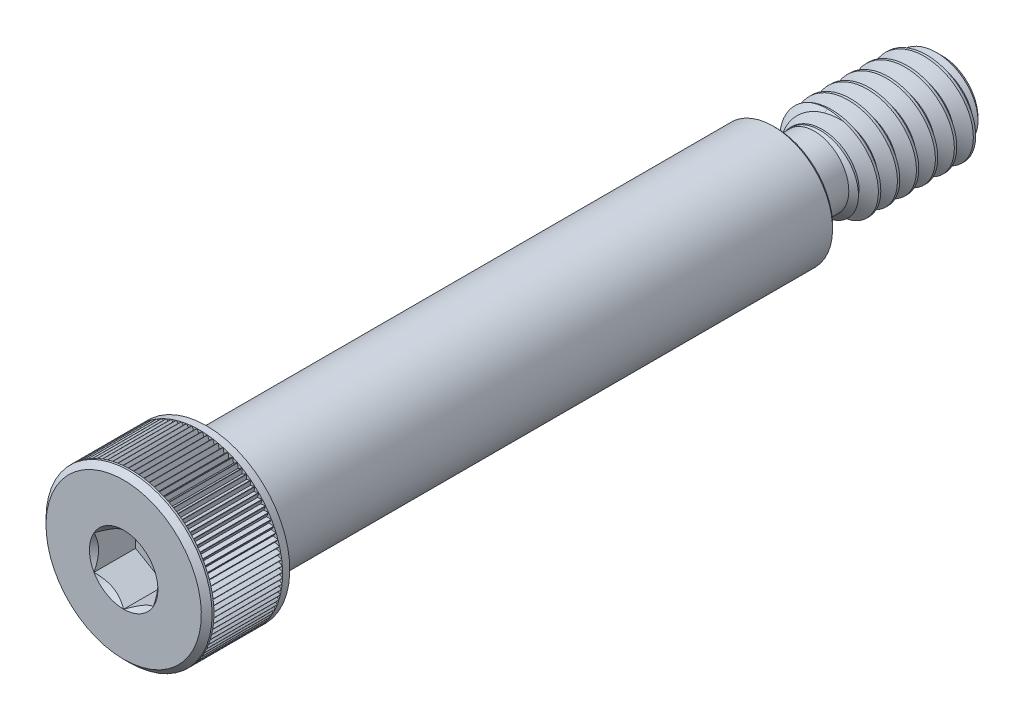
SolidWorks part; units mm, degrees
ref_plane "Front" through (0, 0, 0) normal (0, 0, 1) x (1, 0, 0)
ref_plane "Top" through (0, 0, 0) normal (0, 1, 0) x (1, 0, 0)
ref_plane "Right" through (0, 0, 0) normal (1, 0, 0) x (0, 0, -1)
sketch "Sketch1" plane through (0, 0, 0) normal (1, 0, 0) x (0, 0, -1)
  line L0 (0, 5.5562) -> (5.5562, 5.5562)
  line L1 (5.5562, 5.5562) -> (5.5562, 3.9687)
  line L2 (5.5562, 3.9687) -> (43.6563, 3.9687)
  line L3 (43.6563, 3.9687) -> (43.6563, 3.175)
  line L4 (43.6563, 3.175) -> (54.7688, 3.175)
  line L5 (54.7688, 3.175) -> (54.7687, 0)
  line L6 (54.7687, 0) -> (0, 0)
  line L7 (0, 0) -> (0, 5.5562)
  line L8 (0, 5.5562) -> (0, -5.5563) construction
  line L9 (54.7688, 3.175) -> (54.7687, -3.175) construction
  line L10 (43.6563, 3.9687) -> (43.6563, -3.9688) construction
  line L11 (54.7687, -3.175) -> (53.091, -3.175) construction
  line L12 (24.6062, 0) -> (24.6062, 3.9687) construction
  point P8 (52.8638, -3.175)
  point P12 (43.6563, 0)
  point P17 (9.3662, 3.9687)
  point P18 (24.6062, 0)
  point P19 (24.6062, 3.9687)
  point P20 (39.8462, 3.9687)
  point P21 (39.8462, -3.9688)
  point P22 (9.3662, -3.9688)
  dimension "Head Dia" = 11.1125
  dimension "Head Ht" = 5.5562
  dimension "Thread Lg" = 11.1125
  dimension "Thread Dia" = 6.35
  dimension "Shoulder Dia" = 7.9375
  dimension "Shoulder Lg" = 38.1
  dimension "D1" = 1.905
  dimension "D2" = 1.6778
  dimension "D3" = 19.05
  dimension "D4" = 3.81
revolve "Revolve1" add sketch "Sketch1" angle 360 mid plane about L6
ref_plane "Plane1" through (0, 0, -54.7687) normal (0, 0, 1) x (1, 0, 0)
sketch "Sketch3" plane through (0, 0, -54.7687) normal (0, 0, 1) x (1, 0, 0)
  circle A0 centre (0, 0) radius 3.175
sketch "Sketch5" plane through (0, 0, 0) normal (1, 0, 0) x (0, 0, -1)
  line L0 (43.6563, 3.9687) -> (47.8536, 3.9687)
  line L1 (47.8536, 3.9687) -> (46.1962, 2.3114)
  line L2 (46.1962, 2.3114) -> (44.5199, 2.3114)
  line L3 (43.6563, 3.9687) -> (43.6563, 3.175)
  line L5 (43.6563, 3.175) -> (54.7688, 3.175) construction
  line L6 (54.7687, 0) -> (46.1962, 0) construction
  line L7 (50.4825, 0) -> (50.4825, -3.175) construction
  arc A0 (43.6563, 3.175) -> (44.5199, 2.3114) centre (44.5199, 3.175) ccw
  dimension "D1" = 45
  dimension "CADB" = 2.54
  dimension "CADA" = 4.6228
revolve "Cut-Revolve1" cut sketch "Sketch5" angle 360 mid plane about L6
chamfer "Chamfer1" distance 0.7937 angle 45 1 edges at (0, 3.175, -54.7688)
chamfer "Chamfer2" distance 0.3612 angle 45 1 edges at (0, 5.5562, 0)
chamfer "Chamfer3" distance 0.2032 angle 45 1 edges at (0, 3.9687, -43.6563)
sketch "Sketch10" plane through (0, 0, 0) normal (1, 0, 0) x (0, 0, -1)
  line L0 (0.3612, 0) -> (5.1951, 0) construction
  line L1 (0.3612, -5.5562) -> (0.3612, 5.5562) construction
  line L3 (0.3612, 0) -> (0, 0) construction
  line L4 (5.1951, 0) -> (5.5562, 0) construction
  line L5 (5.5562, -5.5562) -> (5.5562, 5.5562) construction
  point P6 (2.7781, 0)
  dimension "D1" = 4.8339
ref_plane "Plane2" through (0, 0, -2.7781) normal (0, 0, 1) x (1, 0, 0)
sketch "Sketch11" plane through (0, 0, -2.7781) normal (0, 0, 1) x (1, 0, 0)
  line L0 (0, 5.2673) -> (0, 5.5562) construction
  line L1 (0, 5.2673) -> (0.1668, 5.5562)
  line L2 (0, 5.2673) -> (-0.1668, 5.5562)
  line L3 (-0.1668, 5.5562) -> (0.1668, 5.5562)
  line L4 (0, 0) -> (-0.1668, 5.5562) construction
  line L5 (0.1668, 5.5562) -> (0, 0) construction
  circle A1 centre (0, 0) radius 5.5562 construction
  circle A2 centre (0, 0) radius 5.2673 construction
  circle A3 centre (0, 0) radius 5.1951 construction
  point P3 (0, 0.0018)
  point P8 (2.3908, 0.7309)
  dimension "D1" = 0.2889
  dimension "D2" = 3.439
extrude "Cut-Extrude5" cut sketch "Sketch11" against normal mid plane 4.5922
pattern_circular "CirPattern1" count 99 over 360 about axis through (0, 0, -54.7687) along (0, 0, -1) of "Cut-Extrude5"
sketch "Sketch8" plane through (0, 0, 0) normal (0, 0, 1) x (1, 0, 0)
  line L1 (1.9844, 1.1457) -> (0, 2.2914)
  line L2 (0, 2.2914) -> (-1.9844, 1.1457)
  line L3 (-1.9844, 1.1457) -> (-1.9844, -1.1457)
  line L4 (-1.9844, -1.1457) -> (0, -2.2914)
  line L5 (0, -2.2914) -> (1.9844, -1.1457)
  line L6 (1.9844, -1.1457) -> (1.9844, 1.1457)
  circle A0 centre (0, 0) radius 1.9844 construction
  dimension "Hex" = 3.9688
extrude "Cut-Extrude2" cut sketch "Sketch8" against normal blind 2.7781
sketch "Sketch9" plane through (0, 0, 0) normal (0, 0, 1) x (1, 0, 0)
  circle A0 centre (0, 0) radius 2.2914
extrude "Cut-Extrude4" cut sketch "Sketch9" against normal blind 2.7781 draft 45
sketch "Front Sketch" plane through (0, 0, 0) normal (0, 0, 1) x (1, 0, 0)
  line L0 (1.9844, -1.1457) -> (1.9844, 1.1457) construction
  line L1 (-1.9844, 1.1457) -> (-1.9844, -1.1457) construction
  circle A0 centre (0, 0) radius 5.5562 construction
  point P4 (-1.9844, 0)
  point P5 (1.9844, 0)
  point P6 (5.5562, 0)
  point P9 (-5.5562, 0)
ref_plane "Contact Plane 1" through (0, 0, -5.5562) normal (0, 0, -1) x (-1, 0, 0)
ref_axis "Center Axis 1" through (0, 0, -54.7687) along (0, 0, 1)
curve "Helix/Spiral1" pitch 1.27 height 12.3825 radius 3.175 centre (0, 0, -54.7687) axis (0, 0, 1) start towards (0, 1, 0)
sketch "Sketch4" plane through (0, 0, 0) normal (1, 0, 0) x (0, 0, -1)
  line L0 (54.6894, 3.3125) -> (55.9594, 3.3125) construction
  line L1 (55.9594, 3.3125) -> (55.3244, 2.2126) construction
  line L3 (55.3244, 2.2126) -> (54.6894, 3.3125) construction
  line L4 (54.7291, 3.2437) -> (55.9197, 3.2437) construction
  line L5 (54.7688, 3.175) -> (55.88, 3.175) construction
  line L6 (55.245, 2.3501) -> (55.4038, 2.3501) construction
  line L7 (55.3244, 2.3501) -> (55.3244, 2.2126) construction
  line L8 (55.3244, 3.3125) -> (55.3244, 3.175) construction
  line L9 (54.7291, 3.2437) -> (55.9197, 3.2437)
  line L10 (55.9197, 3.2437) -> (55.4038, 2.3501)
  line L11 (55.4038, 2.3501) -> (55.245, 2.3501)
  line L12 (55.245, 2.3501) -> (54.7291, 3.2437)
  point P14 (55.3244, 3.2437)
  point P15 (55.3244, 3.3125)
  dimension "D1" = 1.27
  dimension "D2" = 0.1588
sweep "Cut-Sweep1" cut profiles "Sketch4" path "Helix/Spiral1" align with end faces yes
sketch "Sketch12" plane through (0, 0, 0) normal (1, 0, 0) x (0, 0, -1)
  line L1 (43.6563, 3.7655) -> (43.4531, 3.9687)
  line L2 (43.4531, 3.9687) -> (5.5562, 3.9687)
  line L3 (5.5562, 3.9687) -> (5.5562, 0)
  line L4 (5.5562, -5.5562) -> (5.5562, 5.5562) construction
  line L5 (5.5562, 0) -> (43.6563, 0)
  line L6 (43.6563, 3.7655) -> (43.6563, 3.175)
  line L7 (46.1962, 2.3114) -> (44.5199, 2.3114) construction
  line L8 (46.1962, 2.3114) -> (44.5199, 2.3114)
  line L9 (46.1962, 2.3114) -> (46.1962, 0)
  line L10 (46.1962, 0) -> (43.6563, 0)
  arc A0 (43.6563, 3.175) -> (44.5199, 2.3114) centre (44.5199, 3.175) ccw construction
  arc A1 (43.6563, 3.175) -> (44.5199, 2.3114) centre (44.5199, 3.175) ccw
revolve "Revolve2" add sketch "Sketch12" angle 360 about L5
equation "\"D3@Helix/Spiral1\" = \"Thread Lg@Sketch1\" + \"D4@Helix/Spiral1\""
equation "\"D1@Chamfer1\" = \"Thread Dia@Sketch1\" * .125"
equation "\"D1@Cut-Extrude2\"= \"Head Ht@Sketch1\" * .5"
equation "\"D1@Cut-Extrude4\" = \"D1@Cut-Extrude2\""
equation "\"D1@Chamfer2\" = \"Head Dia@Sketch1\" * .0325"
equation "\"D1@Sketch1\"=\"D4@Helix/Spiral1\"*1.5"
equation "\"D1@Sketch11\"=\"D1@Chamfer2\"*.8"
equation "\"D1@Cut-Extrude5\"=\"D1@Sketch10\"*.95"
equation "\"D1@CirPattern1\"=(360/\"D2@Sketch11\")-6"
equation "\"D3@Sketch1\"=\"Shoulder Lg@Sketch1\"/2"
equation "\"D4@Sketch1\"=\"D3@Sketch1\"*.2"
equation "\"D1@Sketch4\"=\"D4@Helix/Spiral1\""
equation "\"D2@Sketch4\"=\"D1@Sketch4\"/8"
